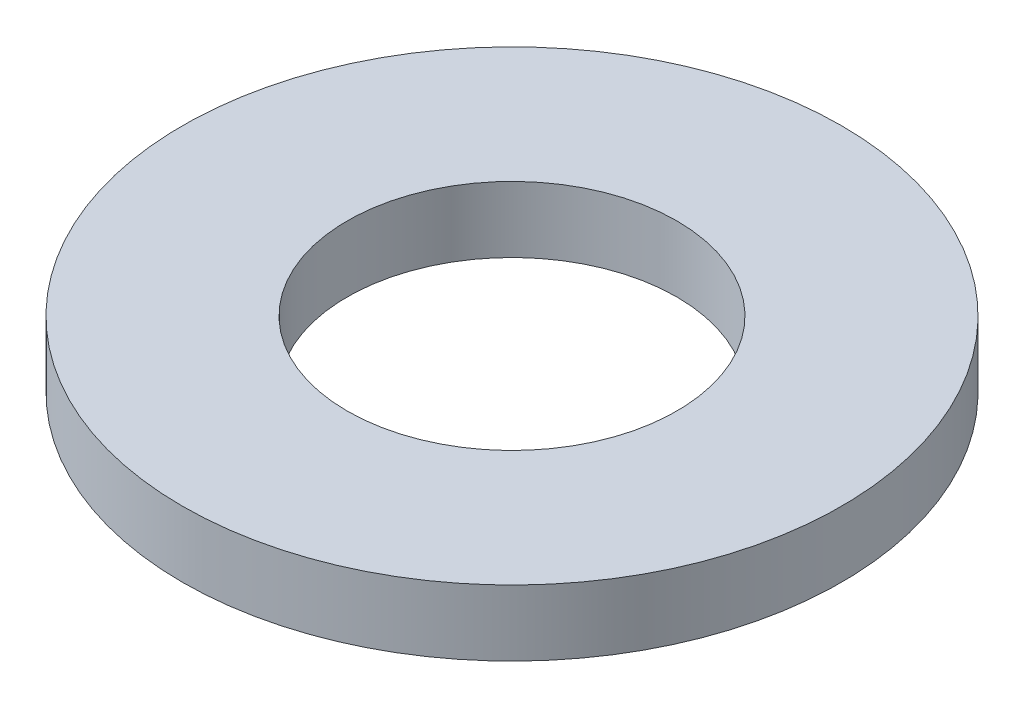
SolidWorks part; units mm, degrees
ref_plane "Front Plane" through (0, 0, 0) normal (0, 0, 1) x (1, 0, 0)
ref_plane "Top Plane" through (0, 0, 0) normal (0, 1, 0) x (1, 0, 0)
ref_plane "Right Plane" through (0, 0, 0) normal (1, 0, 0) x (0, 0, -1)
sketch "Sketch1" plane through (0, 0, 0) normal (0, 1, 0) x (1, 0, 0)
  circle A0 centre (0, 0) radius 35
  dimension "FLANGE_OD" = 70
extrude "Boss-Extrude1" add sketch "Sketch1" along normal blind 7
sketch "Sketch2" plane through (0, 0, 0) normal (0, 1, 0) x (1, 0, 0)
  circle A0 centre (0, 0) radius 17.5
  dimension "BORE_D" = 35
extrude "Cut-Extrude1" cut sketch "Sketch2" along normal through all
sketch "Sketch3" plane through (0, 7, 0) normal (0, 1, 0) x (1, 0, 0)
  circle A0 centre (0, 0) radius 14.4054 construction
  circle A1 centre (-14.4054, 0) radius 2.0816
  dimension "BOLT_D" = 4.1631
  dimension "BOLT_PCD" = 28.8108
extrude "Cut-Extrude2" cut sketch "Sketch3" against normal blind 4.8776 rebuild error yes
pattern_circular "CirPattern1" count 5 over 360 rebuild error yes
